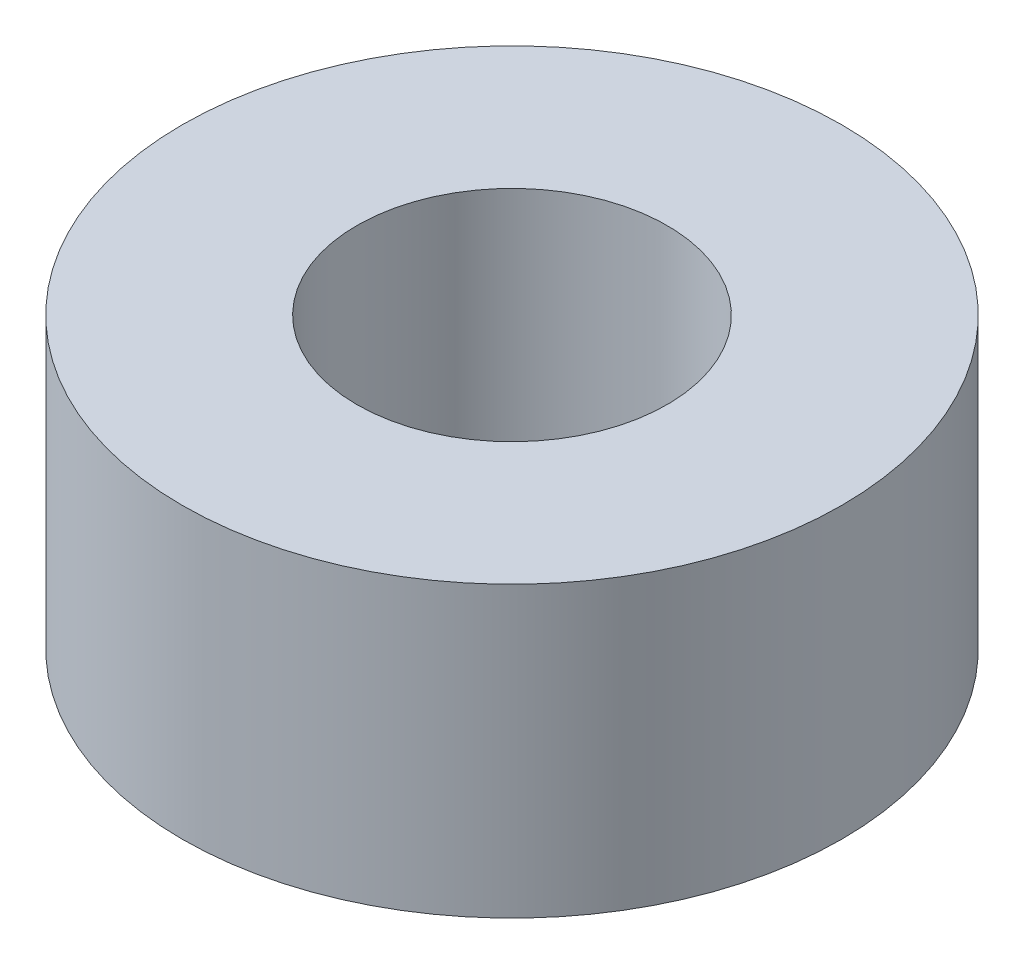
SolidWorks part; units mm, degrees
ref_plane "Front Plane" through (0, 0, 0) normal (0, 0, 1) x (1, 0, 0)
ref_plane "Top Plane" through (0, 0, 0) normal (0, 1, 0) x (1, 0, 0)
ref_plane "Right Plane" through (0, 0, 0) normal (1, 0, 0) x (0, 0, -1)
sketch "Sketch1" plane through (0, 0, 0) normal (0, 1, 0) x (1, 0, 0)
  circle A0 centre (0, 0) radius 2.2
  circle A1 centre (0, 0) radius 4.675
  dimension "D1" = 4.4
  dimension "D2" = 9.35
extrude "Boss-Extrude1" add sketch "Sketch1" along normal blind 4.1
